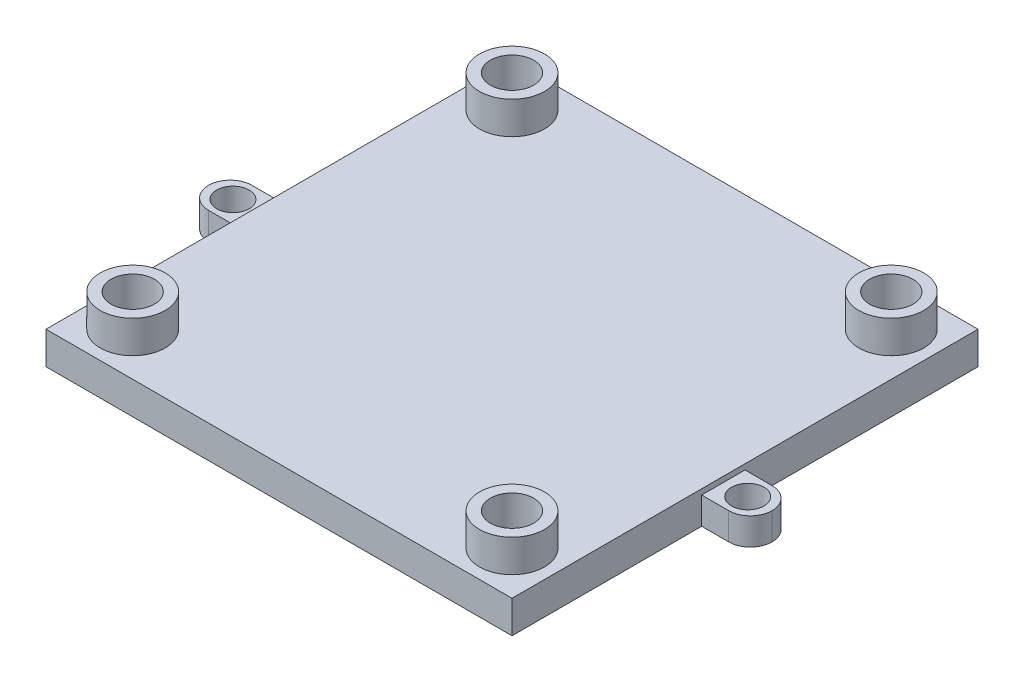
SolidWorks part; units mm, degrees
ref_plane "Front Plane" through (0, 0, 0) normal (0, 0, 1) x (1, 0, 0)
ref_plane "Top Plane" through (0, 0, 0) normal (0, 1, 0) x (1, 0, 0)
ref_plane "Right Plane" through (0, 0, 0) normal (1, 0, 0) x (0, 0, -1)
sketch "Sketch1" plane through (0, 0, 0) normal (0, 1, 0) x (1, 0, 0)
  line L1 (0, 0) -> (43, 0)
  line L2 (0, 0) -> (0, 43)
  line L3 (0, 43) -> (43, 43)
  line L4 (43, 0) -> (43, 43)
  dimension "D1" = 43
  dimension "D2" = 43
extrude "Boss-Extrude1" add sketch "Sketch1" along normal blind 3
sketch "Sketch2" plane through (0, 3, 0) normal (0, 1, 0) x (1, 0, 0)
  line L0 (4, 41) -> (39, 41) construction
  line L1 (43, 43) -> (0, 43) construction
  line L2 (4, 2) -> (39, 2)
  line L3 (0, 0) -> (43, 0) construction
  line L4 (2, 39) -> (2, 4) construction
  line L5 (0, 43) -> (0, 0) construction
  line L6 (41, 39) -> (41, 4) construction
  line L7 (43, 0) -> (43, 43) construction
  circle A0 centre (4, 4) radius 2
  circle A1 centre (39, 4) radius 2
  circle A2 centre (4, 39) radius 2
  circle A3 centre (39, 39) radius 2
  circle A4 centre (4, 39) radius 3
  circle A5 centre (4, 4) radius 3
  circle A6 centre (39, 4) radius 3
  circle A7 centre (39, 39) radius 3
  dimension "D1" = 4
  dimension "D2" = 4
  dimension "D3" = 4
  dimension "D4" = 4
  dimension "D9" = 6
  dimension "D10" = 6
  dimension "D11" = 6
  dimension "D12" = 6
  dimension "D5" = 2
  dimension "D6" = 2
  dimension "D7" = 2
  dimension "D8" = 2
extrude "Boss-Extrude5" add sketch "Sketch2" along normal blind 3 contours A2 | A4
extrude "Boss-Extrude6" add sketch "Sketch2<9>" along normal blind 3 contours A3 | A7
sketch "Sketch2<9>" plane through (0, 3, 0) normal (0, 1, 0) x (1, 0, 0) same geometry as "Sketch2"
extrude "Boss-Extrude7" add sketch "Sketch2<10>" along normal blind 3 contours A0 | A5
sketch "Sketch2<10>" plane through (0, 3, 0) normal (0, 1, 0) x (1, 0, 0) same geometry as "Sketch2"
extrude "Boss-Extrude8" add sketch "Sketch2<11>" along normal blind 3 contours A1 | A6
sketch "Sketch2<11>" plane through (0, 3, 0) normal (0, 1, 0) x (1, 0, 0) same geometry as "Sketch2"
sketch "Sketch3" plane through (0, 0, 0) normal (0, -1, 0) x (1, 0, 0)
  line L0 (0, -43) -> (0, 0) construction
  line L1 (0, -21.5) -> (-4.5, -21.5)
  line L2 (0, -21.5) -> (0, -17.5)
  line L3 (0, -17.5) -> (-4.5, -17.5)
  line L4 (-4.5, -21.5) -> (-4.5, -17.5)
  circle A0 centre (-2.25, -19.5) radius 1.5
  point P6 (-2.25, -17.5)
  point P9 (-4.5, -19.5)
  dimension "D1" = 3
  dimension "D2" = 4
  dimension "D3" = 4.5
extrude "Boss-Extrude9" add sketch "Sketch3" against normal blind 2.5
fillet "Fillet2" radius 2 2 edges at (-4.5, 1.25, -21.5) (-4.5, 1.25, -17.5)
sketch "Sketch4" plane through (0, 0, 0) normal (0, -1, 0) x (1, 0, 0)
  line L0 (43, 0) -> (43, -43) construction
  line L1 (43, -21.5) -> (47.5, -21.5)
  line L2 (43, -21.5) -> (43, -17.5)
  line L3 (43, -17.5) -> (47.5, -17.5)
  line L4 (47.5, -21.5) -> (47.5, -17.5)
  circle A0 centre (45.25, -19.5) radius 1.5
  point P10 (47.5, -19.5)
  point P12 (45.25, -17.5)
  dimension "D3" = 3
  dimension "D1" = 4.5
  dimension "D2" = 4
extrude "Boss-Extrude10" add sketch "Sketch4" against normal blind 2.5
fillet "Fillet3" radius 2 2 edges at (47.5, 1.25, -21.5) (47.5, 1.25, -17.5)
sketch "Sketch7" plane through (0, 3, 0) normal (0, 1, 0) x (1, 0, 0)
  circle A0 centre (4, 39) radius 2
  dimension "D1" = 4
extrude "Cut-Extrude1" cut sketch "Sketch7" against normal through all
extrude "Cut-Extrude2" cut sketch "Sketch2<13>" against normal through all contours A3
sketch "Sketch2<13>" plane through (0, 3, 0) normal (0, 1, 0) x (1, 0, 0) same geometry as "Sketch2"
extrude "Cut-Extrude3" cut sketch "Sketch2<14>" against normal through all contours A0 | A1
sketch "Sketch2<14>" plane through (0, 3, 0) normal (0, 1, 0) x (1, 0, 0) same geometry as "Sketch2"
